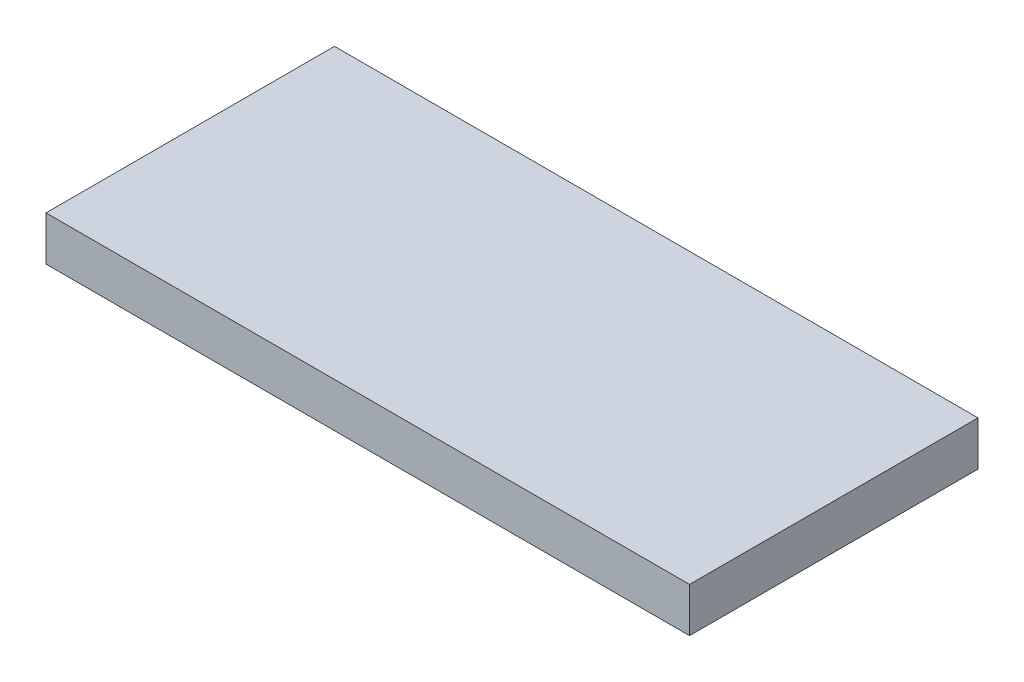
SolidWorks part; units mm, degrees
ref_plane "Front Plane" through (0, 0, 0) normal (0, 0, 1) x (1, 0, 0)
ref_plane "Top Plane" through (0, 0, 0) normal (0, 1, 0) x (1, 0, 0)
ref_plane "Right Plane" through (0, 0, 0) normal (1, 0, 0) x (0, 0, -1)
sketch "Sketch1" plane through (0, 0, 0) normal (0, 1, 0) x (1, 0, 0)
  line L1 (-14.5, -6.5) -> (14.5, -6.5)
  line L2 (-14.5, -6.5) -> (-14.5, 6.5)
  line L3 (-14.5, 6.5) -> (14.5, 6.5)
  line L4 (14.5, -6.5) -> (14.5, 6.5)
  line L5 (-14.5, -6.5) -> (14.5, 6.5) construction
  line L6 (-14.5, 6.5) -> (14.5, -6.5) construction
  point P0 (0, 0)
  dimension "D1" = 29
  dimension "D2" = 13
extrude "Boss-Extrude1" add sketch "Sketch1" along normal blind 2
